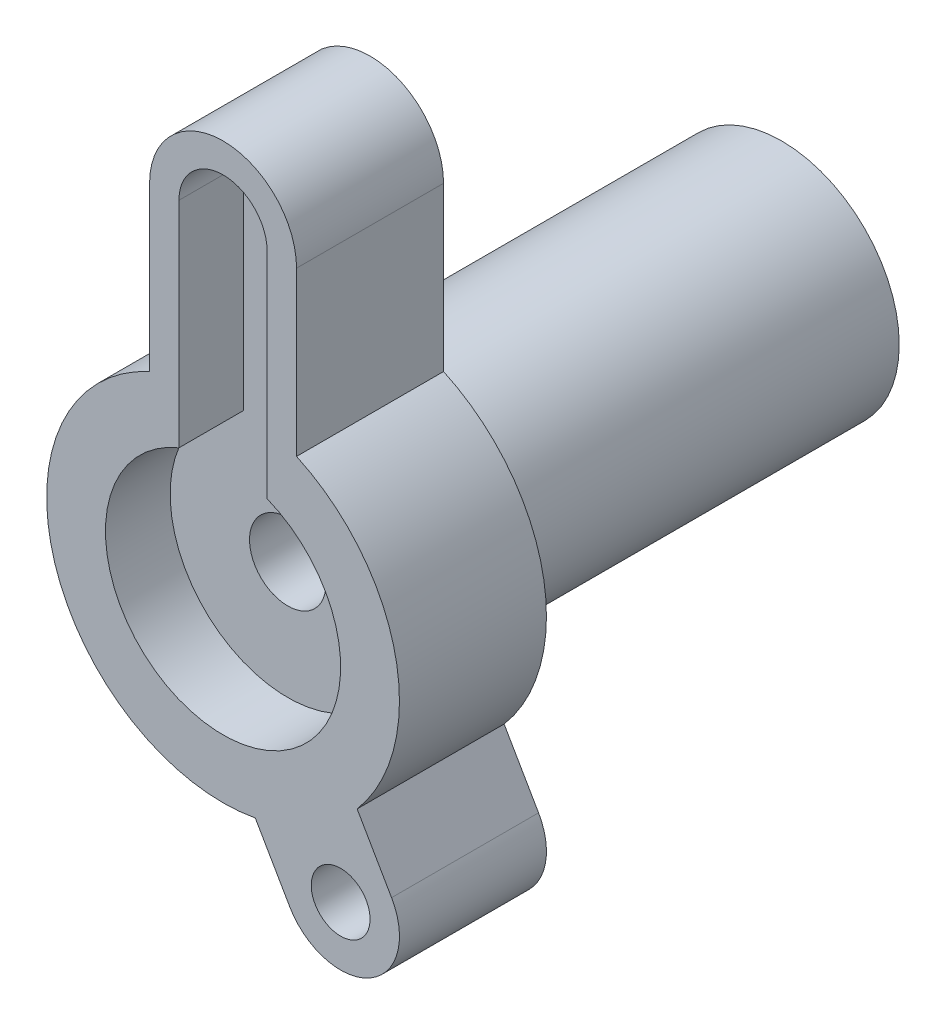
SolidWorks part; units mm, degrees
ref_plane "Спереди" through (0, 0, 0) normal (0, 0, 1) x (1, 0, 0)
ref_plane "Сверху" through (0, 0, 0) normal (0, 1, 0) x (1, 0, 0)
ref_plane "Справа" through (0, 0, 0) normal (1, 0, 0) x (0, 0, -1)
sketch "Эскиз1" plane through (0, 0, 0) normal (0, 0, 1) x (1, 0, 0)
  circle A0 centre (0, 0) radius 20
  circle A1 centre (0, 0) radius 6.5
  dimension "D1" = 40
  dimension "D2" = 13
extrude "Бобышка-Вытянуть1" add sketch "Эскиз1" along normal blind 70
sketch "Эскиз2" plane through (0, 0, 70) normal (0, 0, 1) x (1, 0, 0)
  line L0 (0, 0) -> (0, 55) construction
  line L1 (-12.5, 0) -> (-12.5, 55)
  line L2 (12.5, 0) -> (12.5, 55)
  line L3 (-7.5, 0) -> (-7.5, 55)
  line L4 (7.5, 0) -> (7.5, 55)
  circle A0 centre (0, 0) radius 20 construction
  circle A1 centre (0, 0) radius 20
  circle A2 centre (0, 0) radius 30
  arc A3 (-12.5, 0) -> (12.5, 0) centre (0, 0) ccw
  arc A4 (12.5, 55) -> (-12.5, 55) centre (0, 55) ccw
  arc A5 (7.5, 55) -> (-7.5, 55) centre (0, 55) ccw
  arc A6 (-7.5, 0) -> (7.5, 0) centre (0, 0) ccw
  circle A7 centre (0, 0) radius 6.5 construction
  circle A8 centre (0, 0) radius 6.5
  point P6 (0, 27.5)
  circle M1 centre (0, 0) radius 20
  circle M2 centre (0, 0) radius 6.5
  dimension "D2" = 80
  dimension "D3" = 25
  dimension "D1" = 10
  dimension "D4" = 5
extrude "Бобышка-Вытянуть2" add sketch "Эскиз2" along normal blind 25 separate body contours L1 A2 L2 M1 | L3 A2 L1 M1 | L2 A2 L4 M1 | A5 L4 A2 L2 A4 L1 L3 region at (-9.0194, -18.7754, 70) region at (-10.0431, 22.7208, 70) region at (-12.0264, 41.1359, 70) region at (10.0431, 22.7208, 70)
extrude "Бобышка-Вытянуть4" add sketch "Эскиз2<4>" along normal blind 1 contours A6 L3 L1 A3 L2 L4 M1 | A3 L1 L2 M1 | A1 L3 A6 L4 M2 M1 | A1 L0 A2 L3 | L0 L4 A2 M1 | L4 A5 L3 A2 | A5 L4 A2 L2 A4 L1 L3 | L2 A2 L4 M1 | L1 A2 L2 M1 | L3 A2 L1 M1 region at (3.7605, 19.3243, 70) region at (-3.7807, 24.5974, 70) region at (3.7807, 24.5974, 70) region at (-3.8263, 30.1246, 70) region at (9.9052, 16.9146, 70) region at (10.0431, 22.7208, 70) region at (-10.0431, 22.7208, 70) region at (7.9736, 42.0237, 70) region at (17.545, 8.4283, 70) region at (13.3295, 21.4421, 70)
sketch "Эскиз2<4>" plane through (0, 0, 70) normal (0, 0, 1) x (1, 0, 0) same geometry as "Эскиз2"
sketch "Эскиз3" plane through (0, 0, 95) normal (0, 0, 1) x (1, 0, 0)
  line L0 (0, 0) -> (20, -34.641) construction
  line L1 (8.6603, 5) -> (28.6603, -29.641)
  line L2 (-8.6603, -5) -> (11.3397, -39.641)
  line L3 (0, 0) -> (0, -30) construction
  arc A0 (8.6603, 5) -> (-8.6603, -5) centre (0, 0) ccw
  arc A1 (11.3397, -39.641) -> (28.6603, -29.641) centre (20, -34.641) ccw
  circle A2 centre (0, 0) radius 6.5 construction
  circle A3 centre (0, 0) radius 6.5
  arc A4 (-12.5, 27.2718) -> (12.5, 27.2718) centre (0, 0) ccw construction
  circle A5 centre (20, -34.641) radius 5
  arc A6 (-12.5, 27.2718) -> (12.5, 27.2718) centre (0, 0) ccw
  point P3 (10, -17.3205)
  arc M2 (-12.5, 27.2718) -> (12.5, 27.2718) centre (0, 0) ccw
  dimension "D2" = 10
  dimension "D1" = 30
  dimension "D3" = 40
  dimension "D4" = 20
extrude "Бобышка-Вытянуть5" add sketch "Эскиз3" against normal up to surface (25 mm away) contours L2 A1 L1 A5 M2 region at (25.4272, -24.7436, 95) up to face at (20, 0, 70)
sketch "Эскиз4" plane through (0, 0, 71) normal (0, 0, 1) x (1, 0, 0)
  line L2 (7.5, 18.5405) -> (7.5, 55)
  line L3 (-7.5, 55) -> (-7.5, 18.5405)
  line L4 (7.5, 18.5405) -> (7.5, 55)
  line L5 (-7.5, 55) -> (-7.5, 18.5405)
  circle A0 centre (0, 0) radius 6.5 construction
  circle A1 centre (0, 0) radius 6.5
  arc A2 (-7.5, 18.5405) -> (7.5, 18.5405) centre (0, 0) ccw
  arc A3 (7.5, 55) -> (-7.5, 55) centre (0, 55) ccw
  arc A4 (-7.5, 18.5405) -> (7.5, 18.5405) centre (0, 0) ccw
  arc A5 (7.5, 55) -> (-7.5, 55) centre (0, 55) ccw
  dimension "D1" = 0
extrude "Бобышка-Вытянуть6" add sketch "Эскиз4" along normal blind 13
